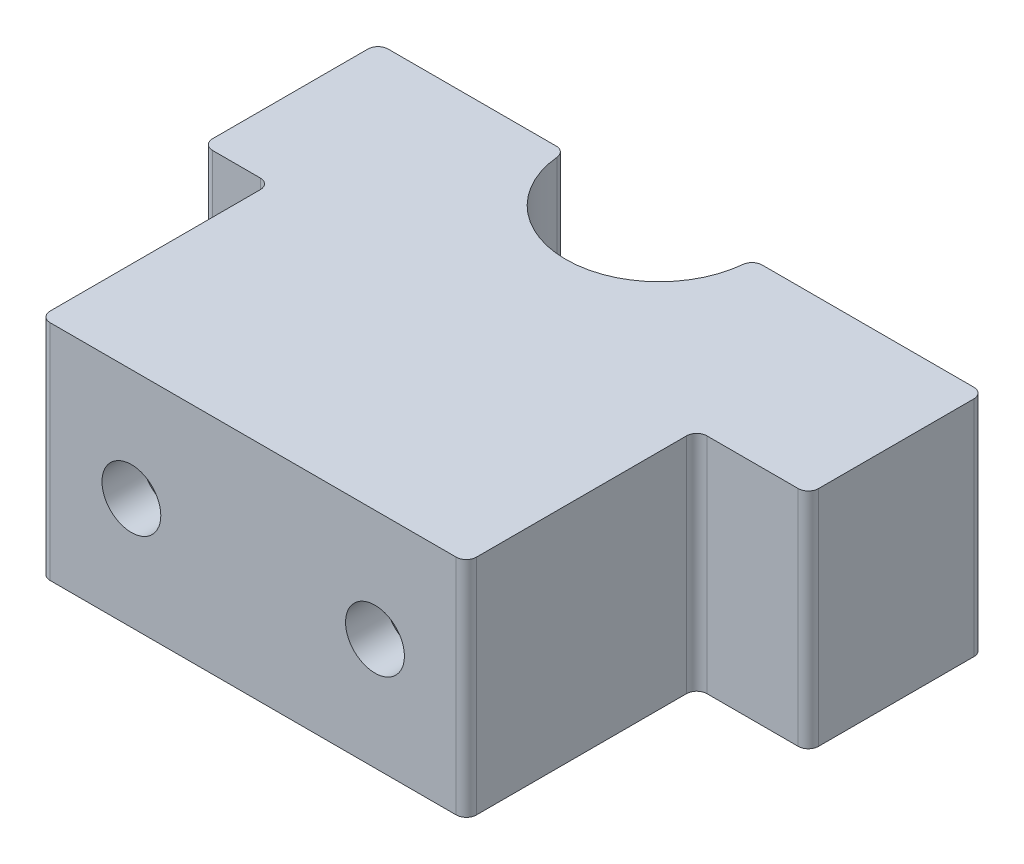
SolidWorks part; units mm, degrees
note: The reader was unsure of these and kept them because the rebuilt part matched: shared geometry of "Sketch1<4>".
ref_plane "Front Plane" through (0, 0, 0) normal (0, 0, 1) x (1, 0, 0)
ref_plane "Top Plane" through (0, 0, 0) normal (0, 1, 0) x (1, 0, 0)
ref_plane "Right Plane" through (0, 0, 0) normal (1, 0, 0) x (0, 0, -1)
sketch "Sketch1" plane through (0, 0, 0) normal (0, 1, 0) x (1, 0, 0)
  line L0 (-4.6, 10) -> (4.6, 10) construction
  line L1 (-10.5, -10) -> (10.5, -10)
  line L2 (-10.5, -10) -> (-10.5, 10)
  line L3 (-10.5, 10) -> (-4.6, 10)
  line L4 (10.5, -10) -> (10.5, 10)
  line L5 (-10.5, -10) -> (10.5, 10) construction
  line L6 (-10.5, 10) -> (10.5, -10) construction
  line L7 (4.6, 10) -> (10.5, 10)
  line L8 (0, 10) -> (0, -10) construction
  line L9 (-10.5, 10) -> (-13.85, 10)
  line L10 (-13.85, 10) -> (-13.85, 1.35)
  line L11 (-13.85, 1.35) -> (-10.5, 1.35)
  line L12 (10.5, 10) -> (16, 10)
  line L13 (16, 10) -> (16, 1.35)
  line L14 (16, 1.35) -> (10.5, 1.35)
  arc A0 (-4.6, 10) -> (4.6, 10) centre (0, 10) ccw
  arc A1 (4.6, 10) -> (-4.6, 10) centre (0, 10) ccw construction
  point P0 (0, 0)
  dimension "D1" = 9.2
  dimension "D2" = 20
  dimension "D3" = 21
  dimension "D4" = 8.65
  dimension "D5" = 3.35
  dimension "D6" = 5.5
extrude "Boss-Extrude1" add sketch "Sketch1" along normal blind 11 contours A0 L3 L2 L1 L4 L7
sketch "Sketch2" plane through (0, 0, 10) normal (0, 0, 1) x (1, 0, 0)
  line L0 (10.5, 5.5) -> (-10.5, 5.5) construction
  line L1 (10.5, 11) -> (10.5, 0) construction
  line L2 (-10.5, 11) -> (-10.5, 0) construction
  circle A0 centre (-6, 5.5) radius 1.45
  circle A1 centre (6, 5.5) radius 1.45
  dimension "D3" = 2.9
  dimension "D4" = 2.9
  dimension "D1" = 12
  dimension "D2" = 4.5
extrude "Cut-Extrude1" cut sketch "Sketch2" against normal blind 8
sketch "Sketch3" plane through (0, 0, -10) normal (0, 0, -1) x (-1, 0, 0)
  line L0 (-10.5, 5.5) -> (10.5, 5.5) construction
  line L1 (-10.5, 11) -> (-10.5, 0) construction
  line L2 (10.5, 11) -> (10.5, 0) construction
  circle A0 centre (-8.1, 5.5) radius 1.2
  circle A1 centre (8.1, 5.5) radius 1.2
  dimension "D1" = 2.4
  dimension "D2" = 2.4
  dimension "D3" = 2.4
  dimension "D4" = 2.4
extrude "Cut-Extrude2" cut sketch "Sketch3" against normal blind 10
ref_plane "Plane1" through (0, 0, -8) normal (0, 0, -1) x (-1, 0, 0)
sketch "Sketch5" plane through (0, 0, -10) normal (0, 0, -1) x (-1, 0, 0)
  line L0 (-4.6, 11) -> (-4.6, 0) construction
  line L1 (-8.1, 3.0751) -> (-7.05, 3.6813) construction
  line L2 (-6, 4.2876) -> (-6, 6.7124)
  line L3 (-6, 6.7124) -> (-8.1, 7.9249)
  line L4 (-8.1, 7.9249) -> (-10.2, 6.7124)
  line L5 (-10.2, 6.7124) -> (-10.2, 4.2876)
  line L6 (-10.2, 4.2876) -> (-9.15, 3.6813) construction
  line L7 (9.15, 3.6813) -> (10.2, 4.2876) construction
  line L8 (10.2, 4.2876) -> (10.2, 6.7124)
  line L9 (10.2, 6.7124) -> (8.1, 7.9249)
  line L10 (8.1, 7.9249) -> (6, 6.7124)
  line L11 (6, 6.7124) -> (6, 4.2876)
  line L12 (7.05, 3.6813) -> (8.1, 3.0751) construction
  line L13 (-4.6, 0) -> (-10.5, 0) construction
  line L14 (-10.5, 11) -> (-10.5, 0) construction
  line L15 (10.5, 11) -> (10.5, 0) construction
  line L16 (-10.2, 4.2876) -> (-10.2, 0)
  line L18 (-10.2, 0) -> (-6, 0)
  line L19 (-6, 0) -> (-6, 4.2876)
  line L20 (6, 4.2876) -> (6, 0)
  line L22 (6, 0) -> (10.2, 0)
  line L23 (10.2, 0) -> (10.2, 4.2876)
  line L24 (6, 4.2876) -> (7.05, 3.6813) construction
  line L25 (8.1, 3.0751) -> (9.15, 3.6813) construction
  line L26 (-7.05, 3.6813) -> (-6, 4.2876) construction
  line L27 (-9.15, 3.6813) -> (-8.1, 3.0751) construction
  line L28 (10.5, 0) -> (4.6, 0) construction
  arc A0 (-6, 5.5) -> (-10.2, 5.5) centre (-8.1, 5.5) ccw construction
  arc A1 (10.2, 5.5) -> (6, 5.5) centre (8.1, 5.5) ccw construction
  arc A2 (6, 5.5) -> (7.05, 3.6813) centre (8.1, 5.5) ccw construction
  arc A3 (7.05, 3.6813) -> (9.15, 3.6813) centre (8.1, 5.5) ccw construction
  arc A4 (9.15, 3.6813) -> (10.2, 5.5) centre (8.1, 5.5) ccw construction
  arc A5 (-7.05, 3.6813) -> (-6, 5.5) centre (-8.1, 5.5) ccw construction
  arc A6 (-9.15, 3.6813) -> (-7.05, 3.6813) centre (-8.1, 5.5) ccw construction
  arc A7 (-10.2, 5.5) -> (-9.15, 3.6813) centre (-8.1, 5.5) ccw construction
  dimension "D1" = 4.2
  dimension "D2" = 1.4
  dimension "D3" = 4.2
extrude "Cut-Extrude3" cut sketch "Sketch5" against normal blind 2.4 from surface at -2
ref_plane "Plane2" through (0, 0, 8) normal (0, 0, 1) x (1, 0, 0)
sketch "Sketch6" plane through (0, 0, 10) normal (0, 0, 1) x (1, 0, 0)
  line L0 (-10.5, 11) -> (-10.5, 0) construction
  line L1 (-6, 8.56) -> (-8.65, 7.03)
  line L2 (-8.65, 7.03) -> (-8.65, 3.97)
  line L3 (-7.325, 3.205) -> (-6, 2.44) construction
  line L4 (-4.675, 3.205) -> (-3.35, 3.97) construction
  line L5 (-3.35, 3.97) -> (-3.35, 7.03)
  line L6 (-3.35, 7.03) -> (-6, 8.56)
  line L7 (-8.65, 3.97) -> (-8.65, 0)
  line L8 (6, 8.56) -> (3.35, 7.03)
  line L9 (3.35, 7.03) -> (3.35, 3.97)
  line L10 (4.675, 3.205) -> (6, 2.44) construction
  line L11 (7.325, 3.205) -> (8.65, 3.97) construction
  line L12 (8.65, 3.97) -> (8.65, 7.03)
  line L13 (8.65, 7.03) -> (6, 8.56)
  line L15 (-8.65, 0) -> (-3.35, 0)
  line L16 (-3.35, 0) -> (-3.35, 3.97)
  line L17 (3.35, 3.97) -> (3.35, 0)
  line L18 (3.35, 0) -> (8.65, 0)
  line L19 (8.65, 0) -> (8.65, 3.97)
  line L20 (10.5, 11) -> (10.5, 0) construction
  line L21 (-8.65, 3.97) -> (-7.325, 3.205) construction
  line L22 (-6, 2.44) -> (-4.675, 3.205) construction
  line L23 (3.35, 3.97) -> (4.675, 3.205) construction
  line L24 (6, 2.44) -> (7.325, 3.205) construction
  line L25 (-10.5, 0) -> (10.5, 0) construction
  arc A0 (-3.35, 5.5) -> (-8.65, 5.5) centre (-6, 5.5) ccw construction
  arc A1 (8.65, 5.5) -> (3.35, 5.5) centre (6, 5.5) ccw construction
  arc A2 (-8.65, 5.5) -> (-7.325, 3.205) centre (-6, 5.5) ccw construction
  arc A3 (-7.325, 3.205) -> (-4.675, 3.205) centre (-6, 5.5) ccw construction
  arc A4 (-4.675, 3.205) -> (-3.35, 5.5) centre (-6, 5.5) ccw construction
  arc A5 (3.35, 5.5) -> (4.675, 3.205) centre (6, 5.5) ccw construction
  arc A6 (4.675, 3.205) -> (7.325, 3.205) centre (6, 5.5) ccw construction
  arc A7 (7.325, 3.205) -> (8.65, 5.5) centre (6, 5.5) ccw construction
  dimension "D1" = 5.3
  dimension "D2" = 5.3
extrude "Cut-Extrude4" cut sketch "Sketch6" against normal blind 2.4 from surface at -2 starting at plane "Plane2"
extrude "Boss-Extrude2" add sketch "Sketch1<4>" along normal through all contours L14 L13 L12 L4 | L10 L11 L2 L9
sketch "Sketch1<4>" plane through (0, 0, 0) normal (0, 1, 0) x (1, 0, 0) same geometry as "Sketch1"
fillet "Fillet2" radius 0.5 10 edges at (-10.5, 5.5, 10) (10.5, 5.5, 10) (-4.6, 5.5, -10) (4.6, 5.5, -10) (-13.85, 5.5, -10) (-13.85, 5.5, -1.35) (-10.5, 5.5, -1.35) (16, 5.5, -1.35) (16, 5.5, -10) (10.5, 5.5, -1.35)
equation "\"D4@Sketch2\"=\"D3@Sketch2\""
equation "\"D4@Sketch3\"=\"D3@Sketch3\""
equation "\"D2@Sketch3\"=\"D1@Sketch3\""
equation "\"D3@Sketch5\"=\"D1@Sketch5\""
equation "\"D2@Sketch6\"=\"D1@Sketch6\""
